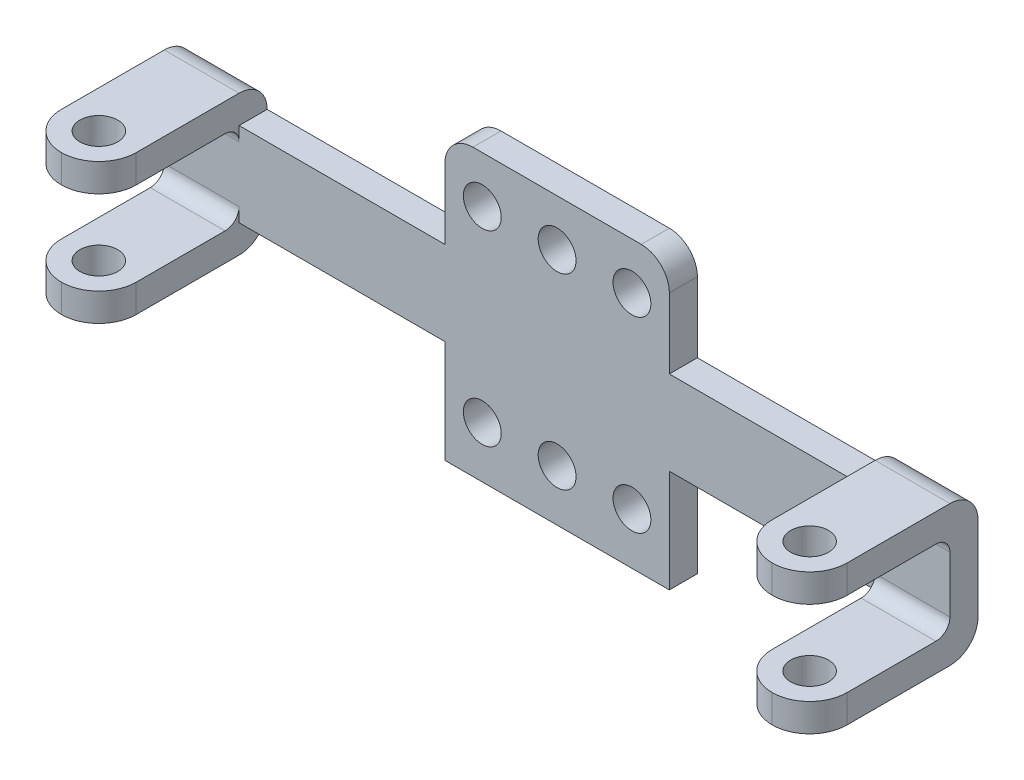
SolidWorks part; units mm, degrees
material "AISI 304"
ref_plane "Front Plane" through (0, 0, 0) normal (0, 0, 1) x (1, 0, 0)
ref_plane "Top Plane" through (0, 0, 0) normal (0, 1, 0) x (1, 0, 0)
ref_plane "Right Plane" through (0, 0, 0) normal (1, 0, 0) x (0, 0, -1)
sketch "Sketch1" plane through (0, 0, 0) normal (0, 1, 0) x (1, 0, 0)
  line L1 (-20, -30) -> (20, -30)
  line L2 (-20, -30) -> (-20, 30)
  line L3 (-20, 30) -> (20, 30)
  line L4 (20, -30) -> (20, 30)
  line L5 (-20, -30) -> (20, 30) construction
  line L6 (-20, 30) -> (20, -30) construction
  point P0 (0, 0)
  dimension "D1" = 40
  dimension "D2" = 60
extrude "Boss-Extrude1" add sketch "Sketch1" along normal blind 3
sketch "Sketch3" plane through (-20, 0, 0) normal (-1, 0, 0) x (0, 0, 1)
  line L5 (-30, 3) -> (-30, 35)
  line L6 (-30, 35) -> (-33, 35)
  line L7 (-33, 35) -> (-33, 0)
  line L8 (-33, 0) -> (-30, 0)
  line L9 (-30, 0) -> (-30, 3)
  dimension "D1" = 35
  dimension "D2" = 3
extrude "Boss-Extrude3" add sketch "Sketch3" against normal blind 50 and the other way blind 10
sketch "Sketch4" plane through (0, 0, -30) normal (0, 0, 1) x (1, 0, 0)
  line L0 (0, 31.8462) -> (0, -2.6446) construction
  line L1 (30, 35) -> (-30, 35) construction
  circle A0 centre (0, 30) radius 2.025
  circle A1 centre (8, 30) radius 2.025
  circle A2 centre (16, 30) radius 2.025
  circle A3 centre (-8, 30) radius 2.025
  circle A4 centre (-16, 30) radius 2.025
  circle A5 centre (-16, 10) radius 2.025
  circle A6 centre (-8, 10) radius 2.025
  circle A7 centre (0, 10) radius 2.025
  circle A8 centre (8, 10) radius 2.025
  circle A9 centre (16, 10) radius 2.025
  dimension "D1" = 4.05
  dimension "D2" = 5
  dimension "D5" = 16
  dimension "D6" = 16
  dimension "D8" = 20
  dimension "D3" = 3
  dimension "D4" = 3
  dimension "D7" = 2
extrude "Cut-Extrude1" cut sketch "Sketch4" against normal through all
sketch "Sketch5" plane through (0, 0, 0) normal (0, -1, 0) x (1, 0, 0)
  line L0 (-20, -30) -> (-20, -33)
  line L1 (-30, -33) -> (30, -33) construction
  line L2 (-20, -33) -> (-30, -33)
  line L3 (-30, -33) -> (-30, -30)
  line L4 (-30, -30) -> (-20, -30) construction
  line L5 (-30, -30) -> (-20, -30)
  line L6 (0, -39.6098) -> (0, 11.9522) construction
  line L7 (30, -33) -> (30, -30)
  line L8 (20, -33) -> (30, -33)
  line L9 (20, -30) -> (20, -33)
  line L10 (30, -30) -> (20, -30)
  dimension "D1" = 10
extrude "Cut-Extrude3" cut sketch "Sketch5" against normal blind 5
fillet "Fillet5" radius 3 1 edges at (0, 0, -33)
fillet "Fillet6" radius 1.5 1 edges at (0, 3, -30)
sketch "Sketch6" plane through (0, 0, -30) normal (0, 0, 1) x (1, 0, 0)
  line L0 (0, 36.5574) -> (0, -2.9321) construction
  line L1 (-12, 35) -> (-12, 5)
  line L2 (-12, 35) -> (-30, 35)
  line L3 (-30, 35) -> (30, 35) construction
  line L4 (-30, 35) -> (-30, 5)
  line L5 (-30, 5) -> (-12, 5)
  line L6 (12, 35) -> (30, 35)
  line L7 (-12, 36.5574) -> (-12, -2.9321) construction
  line L8 (30, 35) -> (30, 5)
  line L9 (30, 5) -> (12, 5)
  line L10 (12, 35) -> (12, 5)
  dimension "D1" = 12
extrude "Cut-Extrude4" cut sketch "Sketch6" against normal through all
sketch "Sketch7" plane through (0, 0, -30) normal (0, 0, 1) x (1, 0, 0)
  line L0 (-8, 30) -> (-8, 10) construction
  line L1 (-8, 20) -> (-28.207, 20) construction
  line L2 (-12, 24.5) -> (-42, 24.5)
  line L3 (-12, 5) -> (-12, 35) construction
  line L4 (-42, 24.5) -> (-42, 15.5)
  line L5 (-42, 15.5) -> (-12, 15.5)
  line L6 (-12, 15.5) -> (-12, 24.5)
  line L7 (0, 36.5719) -> (0, -1.2575) construction
  line L8 (42, 15.5) -> (12, 15.5)
  line L9 (42, 24.5) -> (42, 15.5)
  line L10 (12, 24.5) -> (42, 24.5)
  line L11 (12, 15.5) -> (12, 24.5)
  dimension "D1" = 4.5
  dimension "D2" = 4.5
  dimension "D3" = 30
extrude "Boss-Extrude4" add sketch "Sketch7" against normal blind 3
sketch "Sketch8" plane through (0, 5, 0) normal (0, 1, 0) x (1, 0, 0)
  line L0 (-12, 33) -> (-20, 33)
  line L1 (-20, 33) -> (-20, 28.5)
  line L2 (-20, 28.5) -> (-12, 28.5)
  line L3 (20, 28.5) -> (-20, 28.5) construction
  line L4 (-12, 28.5) -> (-12, 33)
  line L5 (0, 34.6408) -> (0, -32.4899) construction
  line L6 (20, 28.5) -> (12, 28.5)
  line L7 (20, 33) -> (20, 28.5)
  line L8 (12, 33) -> (20, 33)
  line L9 (12, 28.5) -> (12, 33)
extrude "Cut-Extrude5" cut sketch "Sketch8" against normal through all
sketch "Sketch9" plane through (0, 0, -30) normal (0, 0, 1) x (1, 0, 0)
  line L0 (-42, 24.5) -> (-42, 27.5)
  line L1 (-42, 27.5) -> (-34, 27.5)
  line L2 (-34, 27.5) -> (-34, 24.5)
  line L3 (-12, 24.5) -> (-42, 24.5) construction
  line L4 (-34, 24.5) -> (-42, 24.5)
  line L5 (-42, 20) -> (27.3927, 20) construction
  line L6 (-42, 24.5) -> (-42, 15.5) construction
  line L7 (0, 36.6782) -> (0, -2.2114) construction
  line L8 (-34, 12.5) -> (-34, 15.5)
  line L9 (-42, 12.5) -> (-34, 12.5)
  line L10 (-42, 15.5) -> (-42, 12.5)
  line L11 (-34, 15.5) -> (-42, 15.5)
  line L12 (42, 12.5) -> (34, 12.5)
  line L13 (42, 15.5) -> (42, 12.5)
  line L14 (34, 15.5) -> (42, 15.5)
  line L15 (34, 12.5) -> (34, 15.5)
  line L16 (34, 27.5) -> (34, 24.5)
  line L17 (42, 27.5) -> (34, 27.5)
  line L18 (42, 24.5) -> (42, 27.5)
  line L19 (34, 24.5) -> (42, 24.5)
  dimension "D1" = 3
  dimension "D2" = 8
extrude "Boss-Extrude5" add sketch "Sketch9" against normal blind 3 and the other way blind 15
fillet "Fillet7" radius 3 4 edges at (38, 12.5, -33) (-38, 12.5, -33) (38, 27.5, -33) (-38, 27.5, -33)
fillet "Fillet8" radius 1.5 4 edges at (38, 15.5, -30) (-38, 15.5, -30) (38, 24.5, -30) (-38, 24.5, -30)
sketch "Sketch10" plane through (0, 27.5, 0) normal (0, 1, 0) x (1, 0, 0)
  line L0 (-38, 15) -> (-38, 36.0585) construction
  line L1 (-34, 15) -> (-42, 15) construction
  line L3 (0, 34.6974) -> (0, -33.6785) construction
  circle A0 centre (-38, 19) radius 2.025
  circle A1 centre (38, 19) radius 2.025
  dimension "D1" = 4.05
  dimension "D2" = 4
extrude "Cut-Extrude6" cut sketch "Sketch10" against normal blind 16
fillet "Fillet9" radius 4 8 edges at (42, 14, -15) (42, 26, -15) (-34, 14, -15) (-34, 26, -15) (34, 14, -15) (34, 26, -15) (-42, 14, -15) (-42, 26, -15)
fillet "Fillet10" radius 3 6 edges at (20, 1.5, -28.5) (20, 1.5, 30) (-20, 1.5, 30) (-20, 1.5, -28.5) (12, 35, -31.5) (-12, 35, -31.5)
sketch "Sketch11" plane through (0, 0, -30) normal (0, 0, 1) x (1, 0, 0)
  line L0 (-12, 4.5) -> (-24.8434, 4.5)
  line L1 (-24.8434, 4.5) -> (-24.8434, -2.5322)
  line L2 (-24.8434, -2.5322) -> (23.3855, -2.5322)
  line L3 (23.3855, -2.5322) -> (23.3855, 4.5)
  line L4 (23.3855, 4.5) -> (-12, 4.5)
extrude "Cut-Extrude7" cut sketch "Sketch11" against normal blind 10 and the other way through all
